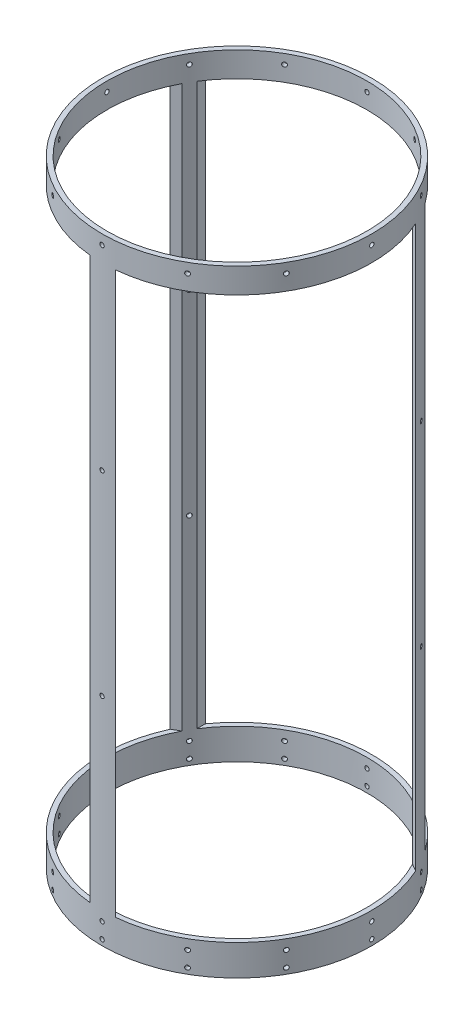
SolidWorks part; units mm, degrees
material "6061-T6 (SS)"
ref_plane "Front Plane" through (0, 0, 0) normal (0, 0, 1) x (1, 0, 0)
ref_plane "Top Plane" through (0, 0, 0) normal (0, 1, 0) x (1, 0, 0)
ref_plane "Right Plane" through (0, 0, 0) normal (1, 0, 0) x (0, 0, -1)
sketch "Sketch1" plane through (0, 0, 0) normal (0, 1, 0) x (1, 0, 0)
  circle A0 centre (0, 0) radius 88.9
  circle A1 centre (0, 0) radius 85.725
  dimension "D1" = 177.8
  dimension "D2" = 171.45
extrude "Boss-Extrude1" add sketch "Sketch1" along normal mid plane 406.4
sketch "Sketch2" plane through (0, 0, 0) normal (0, 0, 1) x (1, 0, 0)
  line L0 (85.725, 203.2) -> (-85.725, 203.2) construction
  line L1 (-72.39, -182.88) -> (72.39, -182.88)
  line L2 (-72.39, -182.88) -> (-72.39, 186.69)
  line L3 (-72.39, 186.69) -> (72.39, 186.69)
  line L4 (72.39, -182.88) -> (72.39, 186.69)
  line L5 (-72.39, -182.88) -> (72.39, 186.69) construction
  line L6 (-72.39, 186.69) -> (72.39, -182.88) construction
  line L7 (88.9, -203.2) -> (88.9, 203.2) construction
  line L8 (-88.9, 203.2) -> (-88.9, -203.2) construction
  line L9 (-88.9, -203.2) -> (88.9, -203.2) construction
  point P0 (0, 0)
  dimension "D1" = 16.51
  dimension "D2" = 16.51
  dimension "D3" = 16.51
  dimension "D4" = 20.32
extrude "Cut-Extrude1" cut sketch "Sketch2" against normal up to surface (51.6033 mm away) up to face at (0, 203.2, 88.9)
pattern_circular "CirPattern1" count 3 over 360 about axis through (0, 203.2, 0) along (0, -1, 0) of "Cut-Extrude1"
ref_plane "Plane1" through (88.9, 0, 0) normal (1, 0, 0) x (0, 0, -1)
sketch "Sketch3" plane through (88.9, 0, 0) normal (1, 0, 0) x (0, 0, -1)
  line L0 (36.8899, -182.88) -> (-88.4932, -182.88) construction
  line L1 (-88.9, -203.2) -> (88.9, -203.2) construction
  circle A0 centre (0, -199.39) radius 1.4351
  circle A1 centre (0, -189.23) radius 1.4351
  dimension "D1" = 3.81
  dimension "D2" = 2.8702
  dimension "D3" = 2.8702
  dimension "D4" = 6.35
extrude "Cut-Extrude2" cut sketch "Sketch3" against normal blind 15.24
pattern_circular "CirPattern2" count 12 over 360 about axis through (0, 203.2, 0) along (0, -1, 0) of "Cut-Extrude2" reverse direction yes
sketch "Sketch4" plane through (88.9, 0, 0) normal (1, 0, 0) x (0, 0, -1)
  line L0 (0, 97.79) -> (0, -97.79) construction
  line L1 (88.9, 203.2) -> (-88.9, 203.2) construction
  circle A0 centre (0, 196.85) radius 1.4351
  dimension "D1" = 2.8702
  dimension "D2" = 6.35
extrude "Cut-Extrude3" cut sketch "Sketch4" against normal blind 15.24
pattern_circular "CirPattern3" count 12 over 360 about axis through (0, 203.2, 0) along (0, -1, 0) of "Cut-Extrude3"
ref_plane "Plane2" through (0, 0, 88.9) normal (0, 0, 1) x (1, 0, 0)
sketch "Sketch5" plane through (0, 0, 88.9) normal (0, 0, 1) x (1, 0, 0)
  circle A0 centre (0, 68.1736) radius 1.4351
  circle A1 centre (0, -60.5536) radius 1.4351
  circle A2 centre (0, 196.85) radius 1.4351 construction
  circle A3 centre (0, -189.23) radius 1.4351 construction
  dimension "D1" = 128.6764
  dimension "D2" = 128.6764
  dimension "D3" = 2.8702
  dimension "D4" = 2.8702
extrude "Cut-Extrude4" cut sketch "Sketch5" against normal blind 35.56
pattern_circular "CirPattern4" count 3 over 360 about axis through (0, 203.2, 0) along (0, -1, 0) of "Cut-Extrude4"
